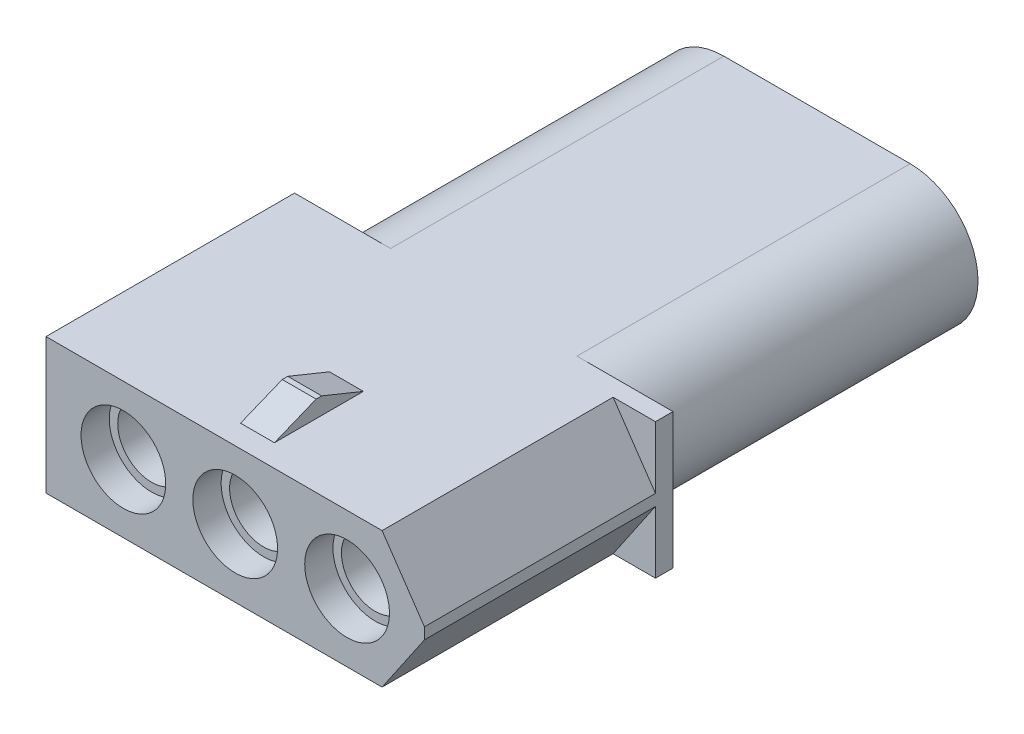
SolidWorks part; units mm, degrees
ref_plane "Front Plane" through (0, 0, 0) normal (0, 0, 1) x (1, 0, 0)
ref_plane "Top Plane" through (0, 0, 0) normal (0, 1, 0) x (1, 0, 0)
ref_plane "Right Plane" through (0, 0, 0) normal (1, 0, 0) x (0, 0, -1)
sketch "Sketch1" plane through (0, 0, 0) normal (0, 0, 1) x (1, 0, 0)
  line L0 (6.604, 3.048) -> (-8.509, 3.048)
  line L1 (-8.509, 3.048) -> (-8.509, -3.048)
  line L2 (-8.509, -3.048) -> (6.604, -3.048)
  line L3 (6.604, -3.048) -> (8.509, -0.254)
  line L4 (8.509, -0.254) -> (8.509, 0.254)
  line L5 (8.509, 0.254) -> (6.604, 3.048)
  line L6 (-8.509, 0) -> (8.509, 0) construction
  dimension "D3" = 1.905
  dimension "D1" = 17.018
  dimension "D2" = 6.096
  dimension "D4" = 0.508
extrude "Boss-Extrude1" add sketch "Sketch1" against normal blind 11.176
ref_plane "Plane1" through (0, 0, -26.162) normal (0, 0, 1) x (1, 0, 0)
sketch "Sketch2" plane through (0, 0, -26.162) normal (0, 0, 1) x (1, 0, 0)
  line L0 (0, 3.048) -> (0, -3.048) construction
  line L1 (-4.191, 3.048) -> (4.191, 3.048)
  line L2 (6.604, 3.048) -> (-8.509, 3.048) construction
  line L3 (-4.191, -3.048) -> (4.191, -3.048)
  line L9 (-5.0292, 0) -> (5.0292, 0) construction
  circle A0 centre (-5.0292, 0) radius 1.524
  circle A1 centre (5.0292, 0) radius 1.524
  arc A2 (-4.191, 3.048) -> (-4.191, -3.048) centre (-4.191, 0) ccw
  arc A3 (4.191, -3.048) -> (4.191, 3.048) centre (4.191, 0) ccw
  circle A4 centre (0, 0) radius 1.524
  dimension "D5" = 3.048
  dimension "D1" = 14.478
  dimension "D6" = 10.0584
extrude "Boss-Extrude2" add sketch "Sketch2" along normal blind 15.7734 separate body
sketch "Sketch3" plane through (0, 0, -10.3886) normal (0, 0, 1) x (1, 0, 0)
  line L6 (6.604, 3.048) -> (-8.509, 3.048)
  line L7 (-8.509, 3.048) -> (-8.509, -3.048)
  line L8 (-8.509, -3.048) -> (6.604, -3.048)
  line L9 (6.604, -3.048) -> (8.509, -0.254)
  line L10 (8.509, -0.254) -> (8.509, 0.254)
  line L11 (8.509, 0.254) -> (6.604, 3.048)
  line L15 (6.604, -3.048) -> (8.509, -0.254)
  line L16 (8.509, -0.254) -> (8.509, 0.254) construction
  line L17 (8.509, 0.254) -> (6.604, 3.048)
  line L18 (6.604, 3.048) -> (8.509, 3.048)
  line L19 (8.509, 3.048) -> (8.509, 0.254)
  line L24 (8.509, -0.254) -> (8.509, -3.048)
  line L25 (8.509, -3.048) -> (6.604, -3.048)
  dimension "D1" = 0
extrude "Boss-Extrude3" add sketch "Sketch3" against normal up to surface (0.7874 mm away) up to face at (2.2013, 0, -11.176)
sketch "Sketch4" plane through (0, 0, -26.162) normal (0, 0, -1) x (-1, 0, 0)
  circle A0 centre (-5.0292, 0) radius 1.6002
  circle A1 centre (5.0292, 0) radius 1.6002
  circle A2 centre (0, 0) radius 1.6002
  dimension "D1" = 3.2004
extrude "Cut-Extrude1" cut sketch "Sketch4" against normal blind 3.048
sketch "Sketch5" plane through (0, 0, 0) normal (0, 0, 1) x (1, 0, 0)
  circle A0 centre (-5.0292, 0) radius 1.524 construction
  circle A1 centre (0, 0) radius 1.524 construction
  circle A2 centre (5.0292, 0) radius 1.524 construction
  circle A3 centre (-5.0292, 0) radius 1.524
  circle A4 centre (0, 0) radius 1.524
  circle A5 centre (5.0292, 0) radius 1.524
extrude "Cut-Extrude2" cut sketch "Sketch5" against normal through all
sketch "Sketch6" plane through (0, 0, 0) normal (0, 0, -1) x (-1, 0, 0)
  circle A0 centre (5.0292, 0) radius 1.905
  circle A1 centre (0, 0) radius 1.905
  circle A2 centre (-5.0292, 0) radius 1.905
  dimension "D1" = 3.81
extrude "Cut-Extrude3" cut sketch "Sketch6" along normal blind 1.27
sketch "Sketch8" plane through (-8.509, 0, 0) normal (-1, 0, 0) x (0, 0, 1)
  line L0 (0, 0) -> (-11.176, 0) construction
  line L1 (-11.176, 3.048) -> (-11.176, -3.048) construction
  line L2 (-5.0013, 3.048) -> (-1.0008, 3.048)
  line L3 (-11.176, 3.048) -> (0, 3.048) construction
  line L4 (-1.0008, 3.048) -> (-2.8766, 3.81)
  line L5 (-2.8766, 3.81) -> (-3.1255, 3.81)
  line L6 (-3.1255, 3.81) -> (-5.0013, 3.048)
  line L7 (-3.1255, -3.81) -> (-5.0013, -3.048)
  line L8 (-2.8766, -3.81) -> (-3.1255, -3.81)
  line L9 (-1.0008, -3.048) -> (-2.8766, -3.81)
  line L10 (-5.0013, -3.048) -> (-1.0008, -3.048)
  line L11 (-3.001, 3.81) -> (-3.001, 3.048) construction
  dimension "D1" = 1.0008
  dimension "D2" = 4.0005
  dimension "D3" = 0.2489
  dimension "D4" = 0.762
extrude "Boss-Extrude4" add sketch "Sketch8" against normal blind 1.524 from offset 7.747 offset against normal yes
sketch "SketchX" plane through (0, 0, 0) normal (1, 0, 0) x (0, 0, -1)
  line L0 (26.162, 4.9454) -> (26.162, -4.9454) construction
  line L1 (-7.112, 3.048) -> (7.2771, 3.048)
  line L2 (-7.112, 3.048) -> (-7.112, -3.048)
  line L5 (17.9451, 3.048) -> (17.9451, 4.318)
  line L6 (10.3886, 3.048) -> (0, 3.048) construction
  line L7 (17.9451, 4.318) -> (7.2771, 4.318)
  line L8 (-7.112, 0) -> (0, 0) construction
  line L9 (7.2771, 4.318) -> (7.2771, 3.048)
  line L10 (17.9451, -3.048) -> (17.9451, -4.318)
  line L11 (17.9451, -4.318) -> (7.2771, -4.318)
  line L12 (7.2771, -4.318) -> (7.2771, -3.048)
  line L13 (-7.112, -3.048) -> (7.2771, -3.048)
  dimension "D1" = 6.096
  dimension "D2" = 33.274
  dimension "D3" = 8.636
  dimension "D4" = 25.0571
  dimension "D5" = 10.668
sketch "SketchZ" plane through (0, 0, 0) normal (0, 0, 1) x (1, 0, 0)
  line L0 (-9.779, 0) -> (9.779, 0) construction
  line L1 (-9.779, 4.318) -> (9.779, 4.318)
  line L2 (-9.779, 4.318) -> (-9.779, -4.318)
  line L3 (-9.779, -4.318) -> (9.779, -4.318)
  line L4 (9.779, 4.318) -> (9.779, -4.318)
  dimension "D1" = 19.558
  dimension "D2" = 8.636
